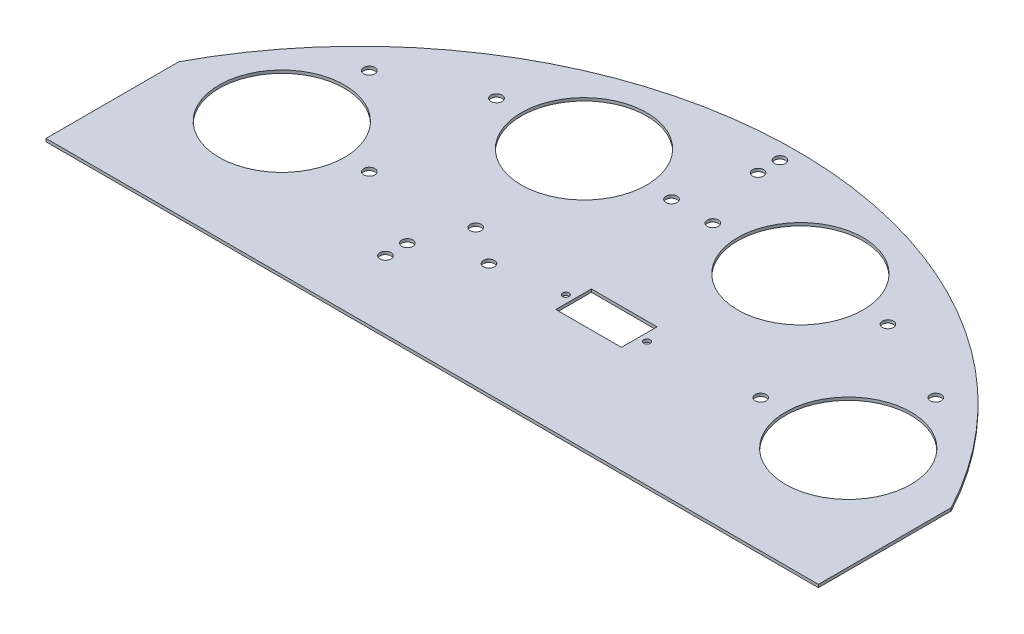
SolidWorks part; units mm, degrees
material "1060 Alloy"
ref_plane "Front Plane" through (0, 0, 0) normal (0, 0, 1) x (1, 0, 0)
ref_plane "Top Plane" through (0, 0, 0) normal (0, 1, 0) x (1, 0, 0)
ref_plane "Right Plane" through (0, 0, 0) normal (1, 0, 0) x (0, 0, -1)
sketch "Sketch3" plane through (0, 0, 0) normal (0, 1, 0) x (1, 0, 0)
  line L5 (-149.8445, -43.9726) -> (150.1555, -43.9726) construction
  line L6 (97.2375, 26.5616) -> (0.1555, -43.9726)
  line L7 (-86.3026, -18.9726) -> (-147.7465, -18.9726)
  line L8 (-132.2262, 26.5616) -> (-132.2262, -18.9726)
  line L9 (86.6136, -18.9726) -> (148.0575, -18.9726)
  line L10 (132.5372, 26.5616) -> (132.5372, -18.9726)
  line L11 (86.6136, -18.9726) -> (-86.3026, -18.9726)
  circle A10 centre (0.1555, -43.9726) radius 120 construction
  circle A11 centre (0.1555, -43.9726) radius 90 construction
  circle A12 centre (0.1555, -43.9726) radius 150
  circle A13 centre (97.2375, 26.5616) radius 21.5
  circle A14 centre (37.2375, 70.1542) radius 21.5
  circle A15 centre (-36.9265, 70.1542) radius 21.5
  circle A16 centre (-96.9265, 26.5616) radius 21.5
  point P5 (0.1555, -43.9726)
  point P9 (0.1555, -43.9726)
  point P22 (0.1555, -43.9726)
  dimension "D3" = 300
  dimension "D7" = 43
  dimension "D4" = 36
  dimension "D5" = 4
  dimension "D2" = 240
  dimension "D1" = 180
  dimension "D6" = 25
extrude "Boss-Extrude3" add sketch "Sketch3" along normal blind 1 contours A13 A11 L9 L10 A12 L8 L7 A16 A15 A14 region at (0.1555, 0, -30.7154)
sketch "Sketch5" plane through (0, 1, 0) normal (0, 1, 0) x (1, 0, 0)
  line L0 (37.2375, 70.1542) -> (-36.9265, 70.1542) construction
  line L1 (-36.9265, 70.1542) -> (-96.9265, 26.5616) construction
  line L2 (37.2375, 70.1542) -> (97.2375, 26.5616) construction
  circle A0 centre (97.2375, 26.5616) radius 30 construction
  circle A1 centre (37.2375, 70.1542) radius 30 construction
  circle A2 centre (-36.9265, 70.1542) radius 30 construction
  circle A3 centre (-96.9265, 26.5616) radius 30 construction
  point P12 (67.2375, 26.5616)
  point P13 (97.2375, 56.5616)
  point P14 (7.2375, 70.1542)
  point P15 (67.2375, 70.1542)
  point P16 (-6.9265, 70.1542)
  point P17 (-66.9265, 70.1542)
  point P18 (-96.9265, 56.5616)
  point P19 (-66.9265, 26.5616)
sketch "Sketch10" plane through (0, 0, 0) normal (0, -1, 0) x (-1, 0, 0)
  line L0 (-28.4264, 17.6232) -> (-16.5209, 17.6232)
  line L1 (-27.5764, 17.6232) -> (-6.7764, 17.6232) construction
  line L2 (-28.4264, 17.6232) -> (-28.4264, 29.8232)
  line L3 (-28.4264, 29.8232) -> (-5.9264, 29.8232)
  line L4 (-5.9264, 29.8232) -> (-5.9264, 17.6232)
  line L5 (-5.9264, 17.6232) -> (-28.4264, 17.6232)
  line L6 (-5.9264, 18.4732) -> (-5.9264, 28.9732) construction
  line L7 (-6.7764, 29.8232) -> (-27.5764, 29.8232) construction
  line L8 (-28.4264, 28.9732) -> (-28.4264, 18.4732) construction
  circle A0 centre (-0.0264, 100.3613) radius 2.5 construction
  circle A1 centre (-0.0313, 92.8613) radius 2.5 construction
  circle A2 centre (39.2014, 4.3732) radius 2.5 construction
  circle A3 centre (39.2014, 11.8732) radius 2.5 construction
  circle A4 centre (19.1543, 19.7949) radius 2.5 construction
  circle A5 centre (32.1421, 28.2546) radius 2.5 construction
  circle A6 centre (-31.0764, 23.7232) radius 1.1
  circle A7 centre (-3.2764, 23.7232) radius 1.1
extrude "Cut-Extrude3" cut sketch "Sketch10" against normal through all contours L5 L4 L3 L2 L0 | A5 | A4 | A3 | A2 | A1 | A0 | A6 | A7 region at (17.1764, 0, -23.7232) region at (31.0764, 0, -23.7232) region at (3.2764, 0, -23.7232)
hole_wizard "#6 Clearance Hole1" positions "Sketch8" profile "Sketch9" hole size "#6" standard "ANSI Inch" end condition through all
sketch "Sketch8" plane through (0, 0, 0) normal (0, -1, 0) x (-1, 0, 0)
  point P0 (-97.2375, 56.5616)
  point P2 (-67.2375, 26.5616)
  point P4 (-67.2375, 70.1542)
  point P6 (-7.2375, 70.1542)
  point P8 (6.9265, 70.1542)
  point P10 (66.9265, 70.1542)
  point P12 (96.9265, 56.5616)
  point P14 (66.9265, 26.5616)
  point P35 (-0.0313, 92.8613)
  point P38 (-0.0264, 100.3613)
  point P41 (39.2014, 4.3732)
  point P44 (39.2014, 11.8732)
  point P47 (32.1421, 28.2546)
  point P50 (19.1543, 19.7949)
sketch "Sketch9" plane through (97.2375, 0, -56.5616) normal (1, 0, 0) x (0, 0, -1)
  line L0 (0, 0) -> (0, 1)
  line L1 (0, 1) -> (1.8986, 1)
  line L2 (1.8986, 1) -> (1.8986, 0)
  line L5 (1.8986, 0) -> (0, 0)
  line L11 (0, -6.35) -> (0, 107.95) construction
  dimension "Thru Hole Dia." = 3.7973
  dimension "Thru Hole Depth" = 1
